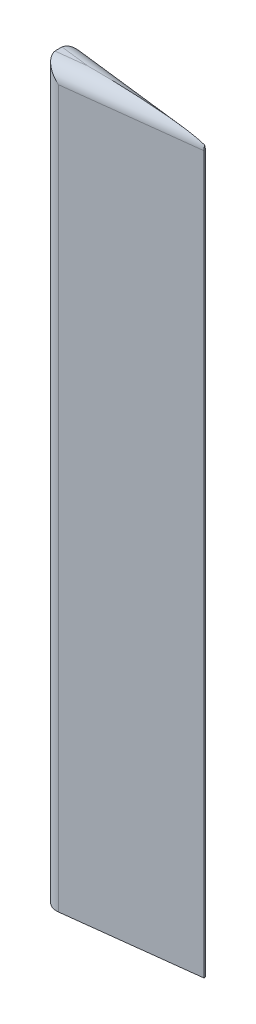
SolidWorks part; units mm, degrees
ref_plane "Front Plane" through (0, 0, 0) normal (0, 0, 1) x (1, 0, 0)
ref_plane "Top Plane" through (0, 0, 0) normal (0, 1, 0) x (1, 0, 0)
ref_plane "Right Plane" through (0, 0, 0) normal (1, 0, 0) x (0, 0, -1)
sketch "Sketch1" plane through (0, 0, 0) normal (0, 0, 1) x (1, 0, 0)
  line L0 (0, 0) -> (0, 100)
  line L1 (20, 0) -> (0, 0)
  line L2 (0, 100) -> (20, 100)
  line L3 (20, 100) -> (20, 0)
  dimension "D1" = 100
  dimension "D2" = 20
extrude "Boss-Extrude1" add sketch "Sketch1" along normal blind 5
sketch "Sketch2" plane through (0, 0, 0) normal (0, 1, 0) x (1, 0, 0)
  line L0 (0, 0) -> (20, -2.4)
  line L4 (20.5161, -2.5) -> (16.2069, -2.5) construction
  line L11 (0, -5) -> (0, 0) construction
  line L12 (20, -5) -> (20, 0) construction
  line L13 (0, -5) -> (20, -2.6)
  line L14 (20, -5) -> (0, -5) construction
  line L15 (20, -5) -> (20, -2.6)
  line L16 (20, -5) -> (0, -5)
  line L18 (20, -2.4) -> (20, 0)
  line L19 (20, 0) -> (0, 0)
  point P14 (0, -2.5)
  dimension "D1" = 0.2
extrude "Cut-Extrude1" cut sketch "Sketch2" against normal through all both and the other way through all
fillet "Fillet1" radius 2 4 edges at (10, 100, 1.2) (10, 100, 3.8)
equation "\"height\"=100"
equation "\"D1@Sketch1\"=\"height\""
equation "\"width\"=20"
equation "\"D2@Sketch1\"=\"width\""
